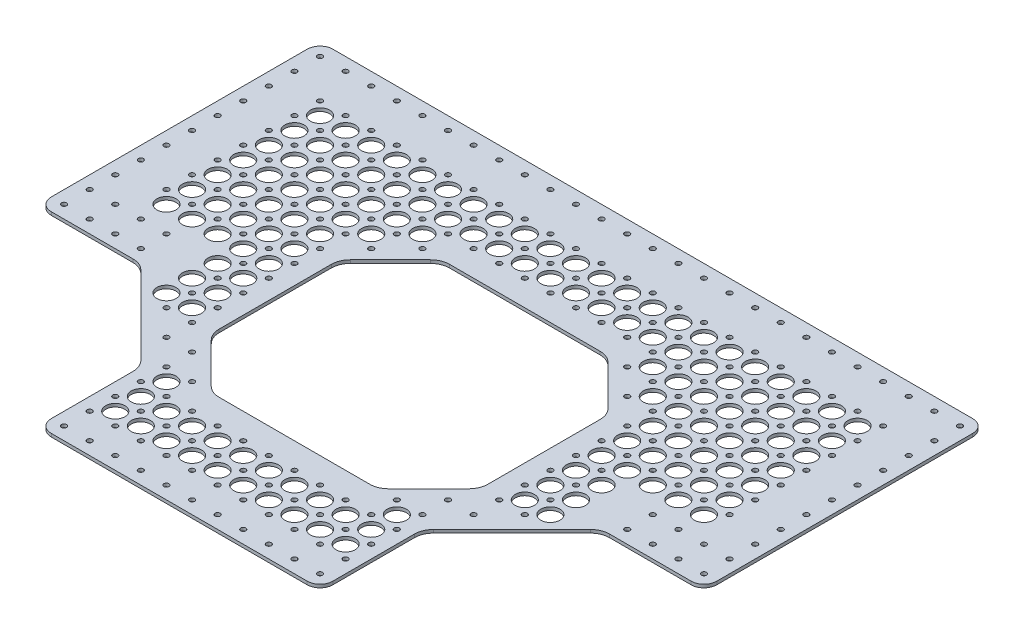
SolidWorks part; units mm, degrees
material "6061 Alloy"
ref_plane "Front Plane" through (0, 0, 0) normal (0, 0, 1) x (1, 0, 0)
ref_plane "Top Plane" through (0, 0, 0) normal (0, 1, 0) x (1, 0, 0)
ref_plane "Right Plane" through (0, 0, 0) normal (1, 0, 0) x (0, 0, -1)
sketch "Sketch1" plane through (0, 0, 0) normal (0, 1, 0) x (1, 0, 0)
  line L0 (0, 0) -> (0, 101.6)
  line L1 (0, 101.6) -> (279.4, 101.6)
  line L2 (279.4, 101.6) -> (279.4, 0)
  line L3 (279.4, 0) -> (368.3045, -88.9045)
  line L4 (368.3045, -88.9045) -> (469.9045, -88.9045)
  line L5 (469.9045, -88.9045) -> (469.9045, -419.1045)
  line L6 (469.9045, -419.1045) -> (368.3045, -419.1045)
  line L7 (368.3045, -419.1045) -> (279.4, -508.0091)
  line L8 (279.4, -508.0091) -> (279.4, -609.6091)
  line L9 (279.4, -609.6091) -> (0, -609.6091)
  line L10 (0, -609.6091) -> (0, -508.0091)
  line L11 (0, -508.0091) -> (-88.9045, -419.1045)
  line L12 (-88.9045, -419.1045) -> (-190.5045, -419.1045)
  line L13 (-190.5045, -419.1045) -> (-190.5045, -88.9045)
  line L14 (-190.5045, -88.9045) -> (-88.9045, -88.9045)
  line L15 (-88.9045, -88.9045) -> (0, 0)
  line L16 (-190.5045, -88.9045) -> (-177.8045, -88.9045)
  line L17 (-177.8045, -88.9045) -> (-177.8045, -419.1045) construction
  line L18 (-177.8045, -419.1045) -> (-190.5045, -419.1045)
  line L19 (-177.8045, -101.6045) -> (-177.8045, -127.0045) construction
  line L20 (139.7, -898.4) -> (139.7, 49101.6) construction
  line L21 (-966.4523, 88.9) -> (49033.5477, 88.9) construction
  line L22 (12.7, 88.9) -> (38.1, 88.9) construction
  line L23 (-1190.5045, -254.0045) -> (48809.4955, -254.0045) construction
  line L24 (-190.5045, -368.3045) -> (-88.9045, -368.3045) construction
  line L25 (-88.9045, -368.3045) -> (-88.9045, -419.1045) construction
  line L26 (-101.6045, -406.4045) -> (-127.0045, -406.4045) construction
  line L27 (-101.6045, -381.0045) -> (-127.0045, -381.0045) construction
  line L28 (-1102.5698, -114.3045) -> (48897.4302, -114.3045) construction
  line L29 (-1089.6596, -165.1045) -> (48910.3404, -165.1045) construction
  line L30 (-177.8045, -127.0045) -> (-152.4045, -127.0045) construction
  circle A0 centre (-177.8045, -101.6045) radius 2.54
  circle A1 centre (-177.8045, -127.0045) radius 2.54
  circle A2 centre (-177.8045, -152.4045) radius 2.54
  circle A3 centre (-177.8045, -177.8045) radius 2.54
  circle A4 centre (-177.8045, -203.2045) radius 2.54
  circle A5 centre (-177.8045, -228.6045) radius 2.54
  circle A6 centre (-177.8045, -254.0045) radius 2.54
  circle A7 centre (-177.8045, -279.4045) radius 2.54
  circle A8 centre (-177.8045, -304.8045) radius 2.54
  circle A9 centre (-177.8045, -330.2045) radius 2.54
  circle A10 centre (-177.8045, -355.6045) radius 2.54
  circle A11 centre (-177.8045, -381.0045) radius 2.54
  circle A12 centre (-177.8045, -406.4045) radius 2.54
  circle A13 centre (457.2045, -406.4045) radius 2.54
  circle A14 centre (457.2045, -381.0045) radius 2.54
  circle A15 centre (457.2045, -355.6045) radius 2.54
  circle A16 centre (457.2045, -330.2045) radius 2.54
  circle A17 centre (457.2045, -304.8045) radius 2.54
  circle A18 centre (457.2045, -279.4045) radius 2.54
  circle A19 centre (457.2045, -254.0045) radius 2.54
  circle A20 centre (457.2045, -228.6045) radius 2.54
  circle A21 centre (457.2045, -152.4045) radius 2.54
  circle A22 centre (457.2045, -177.8045) radius 2.54
  circle A23 centre (457.2045, -203.2045) radius 2.54
  circle A24 centre (457.2045, -127.0045) radius 2.54
  circle A25 centre (457.2045, -101.6045) radius 2.54
  circle A26 centre (12.7, 88.9) radius 2.54
  circle A27 centre (38.1, 88.9) radius 2.54
  circle A28 centre (63.5, 88.9) radius 2.54
  circle A29 centre (88.9, 88.9) radius 2.54
  circle A30 centre (114.3, 88.9) radius 2.54
  circle A31 centre (139.7, 88.9) radius 2.54
  circle A32 centre (165.1, 88.9) radius 2.54
  circle A33 centre (190.5, 88.9) radius 2.54
  circle A34 centre (215.9, 88.9) radius 2.54
  circle A35 centre (241.3, 88.9) radius 2.54
  circle A36 centre (266.7, 88.9) radius 2.54
  circle A37 centre (266.7, -596.9091) radius 2.54
  circle A38 centre (241.3, -596.9091) radius 2.54
  circle A39 centre (215.9, -596.9091) radius 2.54
  circle A40 centre (190.5, -596.9091) radius 2.54
  circle A41 centre (165.1, -596.9091) radius 2.54
  circle A42 centre (139.7, -596.9091) radius 2.54
  circle A43 centre (114.3, -596.9091) radius 2.54
  circle A44 centre (88.9, -596.9091) radius 2.54
  circle A45 centre (63.5, -596.9091) radius 2.54
  circle A46 centre (38.1, -596.9091) radius 2.54
  circle A47 centre (12.7, -596.9091) radius 2.54
  circle A48 centre (-101.6045, -381.0045) radius 2.54
  circle A49 centre (-101.6045, -406.4045) radius 2.54
  circle A50 centre (381.0045, -406.4045) radius 2.54
  circle A51 centre (381.0045, -381.0045) radius 2.54
  circle A52 centre (-127.0045, -406.4045) radius 2.54
  circle A53 centre (-152.4045, -406.4045) radius 2.54
  circle A54 centre (-127.0045, -381.0045) radius 2.54
  circle A55 centre (-152.4045, -381.0045) radius 2.54
  circle A56 centre (431.8045, -381.0045) radius 2.54
  circle A57 centre (406.4045, -381.0045) radius 2.54
  circle A58 centre (431.8045, -406.4045) radius 2.54
  circle A59 centre (406.4045, -406.4045) radius 2.54
  circle A60 centre (-152.4045, -127.0045) radius 2.54
  circle A61 centre (-152.4045, -152.4045) radius 2.54
  circle A62 centre (-127.0045, -127.0045) radius 2.54
  circle A63 centre (-127.0045, -152.4045) radius 2.54
  circle A64 centre (-101.6045, -127.0045) radius 2.54
  circle A65 centre (-101.6045, -152.4045) radius 2.54
  circle A66 centre (-76.2045, -127.0045) radius 2.54
  circle A67 centre (-76.2045, -152.4045) radius 2.54
  circle A68 centre (-50.8045, -127.0045) radius 2.54
  circle A69 centre (-50.8045, -152.4045) radius 2.54
  circle A70 centre (-25.4045, -127.0045) radius 2.54
  circle A71 centre (-25.4045, -152.4045) radius 2.54
  circle A72 centre (-0.0045, -127.0045) radius 2.54
  circle A73 centre (-0.0045, -152.4045) radius 2.54
  circle A74 centre (25.3955, -127.0045) radius 2.54
  circle A75 centre (25.3955, -152.4045) radius 2.54
  circle A76 centre (50.7955, -127.0045) radius 2.54
  circle A77 centre (50.7955, -152.4045) radius 2.54
  circle A78 centre (76.1955, -127.0045) radius 2.54
  circle A79 centre (76.1955, -152.4045) radius 2.54
  circle A80 centre (101.5955, -127.0045) radius 2.54
  circle A81 centre (101.5955, -152.4045) radius 2.54
  circle A82 centre (126.9955, -127.0045) radius 2.54
  circle A83 centre (126.9955, -152.4045) radius 2.54
  circle A84 centre (152.3955, -127.0045) radius 2.54
  circle A85 centre (152.3955, -152.4045) radius 2.54
  circle A86 centre (177.7955, -127.0045) radius 2.54
  circle A87 centre (177.7955, -152.4045) radius 2.54
  circle A88 centre (203.1955, -127.0045) radius 2.54
  circle A89 centre (203.1955, -152.4045) radius 2.54
  circle A90 centre (228.5955, -127.0045) radius 2.54
  circle A91 centre (228.5955, -152.4045) radius 2.54
  circle A92 centre (253.9955, -127.0045) radius 2.54
  circle A93 centre (253.9955, -152.4045) radius 2.54
  circle A94 centre (279.3955, -127.0045) radius 2.54
  circle A95 centre (279.3955, -152.4045) radius 2.54
  circle A96 centre (304.7955, -127.0045) radius 2.54
  circle A97 centre (304.7955, -152.4045) radius 2.54
  circle A98 centre (330.1955, -127.0045) radius 2.54
  circle A99 centre (330.1955, -152.4045) radius 2.54
  circle A100 centre (355.5955, -127.0045) radius 2.54
  circle A101 centre (355.5955, -152.4045) radius 2.54
  circle A102 centre (380.9955, -127.0045) radius 2.54
  circle A103 centre (380.9955, -152.4045) radius 2.54
  circle A104 centre (406.3955, -127.0045) radius 2.54
  circle A105 centre (406.3955, -152.4045) radius 2.54
  circle A106 centre (431.7955, -127.0045) radius 2.54
  circle A107 centre (431.7955, -152.4045) radius 2.54
  point P50 (139.7, 101.6)
  point P105 (-190.5045, -254.0045)
  dimension "D11" = 5.08
  dimension "D16" = 5.08
  dimension "D21" = 5.08
  dimension "D22" = 5.08
  dimension "D1" = 135
  dimension "D2" = 135
  dimension "D3" = 135
  dimension "D4" = 135
  dimension "D5" = 101.6
  dimension "D6" = 279.4
  dimension "D7" = 330.2
  dimension "D8" = 101.6
  dimension "D9" = 125.73
  dimension "D10" = 12.7
  dimension "D12" = 12.7
  dimension "D13" = 25.4
  dimension "D15" = 12.7
  dimension "D17" = 12.7
  dimension "D18" = 25.4
  dimension "D19" = 101.6
  dimension "D20" = 50.8
  dimension "D23" = 12.7
  dimension "D24" = 12.7
  dimension "D25" = 12.7
  dimension "D26" = 12.7
  dimension "D27" = 25.4
  dimension "D28" = 25.4
  dimension "D29" = 25.4
  dimension "D30" = 50.8
  dimension "D31" = 25.4
  dimension "D14" = 13
extrude "Boss-Extrude1" add sketch "Sketch1" along normal blind 3.175 contours L15 L14 L13 L12 L11 L10 L9 L8 L7 L6 L5 L4 L3 L2 L1 L0 A107 A106 A105 A104 A103 A102 A101 A100 A99 A98 A97 A96 A95 A94 A93 A92 region at (139.7, 0, 254.2329)
sketch "Sketch2" plane through (0, 0, -101.6) normal (0, 0, -1) x (-1, 0, 0)
  line L1 (-510.5355, -12.7) -> (251.4645, -12.7)
  line L2 (-510.5355, -12.7) -> (-510.5355, 12.7)
  line L3 (-510.5355, 12.7) -> (251.4645, 12.7)
  line L4 (251.4645, -12.7) -> (251.4645, 12.7)
  line L5 (-510.5355, -12.7) -> (251.4645, 12.7) construction
  line L6 (-510.5355, 12.7) -> (251.4645, -12.7) construction
  point P0 (-129.5355, 0)
  dimension "D1" = 762
  dimension "D2" = 25.4
extrude "Cut-Extrude1" cut sketch "Sketch2" against normal blind 241.3
sketch "Sketch3" plane through (0, 3.175, 0) normal (0, 1, 0) x (1, 0, 0)
  line L0 (-990.1544, -317.5045) -> (49009.8456, -317.5045) construction
  line L1 (-88.9045, -419.1045) -> (-190.5045, -419.1045) construction
  line L2 (-925.1076, -514.3545) -> (49074.8924, -514.3545) construction
  line L3 (139.7, 330.1887) -> (139.7, -609.6091) construction
  line L12 (6.35, -495.3045) -> (273.05, -495.3045)
  line L13 (279.4, -609.6091) -> (0, -609.6091) construction
  line L14 (0, -609.6091) -> (0, -508.0091) construction
  line L15 (6.35, -495.3045) -> (6.35, -317.5045)
  line L16 (6.35, -317.5045) -> (273.05, -317.5045)
  line L17 (273.05, -495.3045) -> (273.05, -317.5045)
  line L18 (6.35, -495.3045) -> (273.05, -317.5045) construction
  line L19 (6.35, -317.5045) -> (273.05, -495.3045) construction
  point P5 (139.7, -406.4045)
  point P9 (139.7, -139.7102)
  point P19 (139.7, -139.7102)
  dimension "D1" = 101.6
  dimension "D2" = 95.25
  dimension "D3" = 177.8
  dimension "D4" = 266.7
  dimension "D6" = 139.7
extrude "Cut-Extrude2" cut sketch "Sketch3" against normal blind 3.175
sketch "Sketch4" plane through (0, 3.175, 0) normal (0, 1, 0) x (1, 0, 0)
  line L0 (222.25, -495.3045) -> (273.05, -444.5045)
  line L1 (6.35, -495.3045) -> (273.05, -495.3045) construction
  line L2 (273.05, -495.3045) -> (273.05, -317.5045) construction
  line L3 (222.25, -495.3045) -> (273.05, -495.3045)
  line L4 (273.05, -495.3045) -> (273.05, -444.5045)
  line L5 (139.7, 369.2915) -> (139.7, -648.6915) construction
  line L7 (279.4, -508.0091) -> (279.4, -609.6091) construction
  line L8 (6.35, -495.3045) -> (6.35, -444.5045)
  line L9 (57.15, -495.3045) -> (6.35, -495.3045)
  line L10 (57.15, -495.3045) -> (6.35, -444.5045)
  point P10 (139.7, -139.7)
  dimension "D1" = 135
  dimension "D2" = 50.8
  dimension "D3" = 139.7
extrude "Boss-Extrude2" add sketch "Sketch4" against normal blind 3.175
sketch "Sketch7" plane through (0, 3.175, 0) normal (0, 1, 0) x (1, 0, 0)
  line L0 (6.35, -317.5045) -> (57.15, -266.7045)
  line L1 (57.15, -266.7045) -> (222.25, -266.7045)
  line L2 (222.25, -266.7045) -> (273.05, -317.5045)
  line L3 (273.05, -317.5045) -> (6.35, -317.5045) construction
  line L4 (6.35, -317.5045) -> (273.05, -317.5045)
  dimension "D1" = 165.1
  dimension "D2" = 45
  dimension "D3" = 45
extrude "Cut-Extrude3" cut sketch "Sketch7" against normal blind 3.175
sketch "Sketch8" plane through (0, 3.175, 0) normal (0, 1, 0) x (1, 0, 0)
  line L0 (-88.9045, -419.1045) -> (-190.5045, -419.1045) construction
  line L1 (0, -609.6091) -> (0, -508.0091) construction
  line L2 (12.7, -596.9091) -> (12.7, -571.5091) construction
  line L3 (279.4, -508.0091) -> (279.4, -609.6091) construction
  line L4 (76.1955, -533.4) -> (101.5955, -533.4) construction
  line L5 (292.1, -292.1091) -> (292.1, -317.5091) construction
  line L6 (-190.5045, -419.1045) -> (-190.5045, -139.7) construction
  line L7 (-190.5045, -139.7) -> (469.9045, -139.7) construction
  line L8 (-127.0045, -203.2) -> (-101.6045, -203.2) construction
  line L9 (-127.0045, -203.2) -> (-127.0045, -228.6) construction
  line L10 (-25.4045, -381) -> (-50.8045, -381) construction
  line L11 (50.7955, -533.4) -> (25.3955, -533.4) construction
  line L12 (228.5955, -533.4) -> (253.9955, -533.4) construction
  line L13 (25.3955, -533.4) -> (25.3955, -508) construction
  line L14 (253.9955, -533.4) -> (253.9955, -508) construction
  line L15 (330.1955, -431.8) -> (304.7955, -431.8) construction
  line L16 (304.7955, -279.4) -> (279.3955, -279.4) construction
  circle A0 centre (12.7, -596.9091) radius 2.54
  circle A1 centre (12.7, -571.5091) radius 2.54
  circle A2 centre (12.7, -546.1091) radius 2.54
  circle A3 centre (12.7, -520.7091) radius 2.54
  circle A4 centre (12.7, -495.3091) radius 2.54
  circle A5 centre (12.7, -469.9091) radius 2.54
  circle A12 centre (12.7, -292.1091) radius 2.54
  circle A13 centre (12.7, -266.7091) radius 2.54
  circle A14 centre (12.7, -241.3091) radius 2.54
  circle A15 centre (12.7, -215.9091) radius 2.54
  circle A16 centre (12.7, -190.5091) radius 2.54
  circle A19 centre (38.1, -190.5091) radius 2.54
  circle A20 centre (38.1, -215.9091) radius 2.54
  circle A21 centre (38.1, -241.3091) radius 2.54
  circle A22 centre (38.1, -266.7091) radius 2.54
  circle A30 centre (38.1, -495.3091) radius 2.54
  circle A31 centre (38.1, -520.7091) radius 2.54
  circle A32 centre (38.1, -546.1091) radius 2.54
  circle A33 centre (38.1, -571.5091) radius 2.54
  circle A35 centre (63.5, -190.5091) radius 2.54
  circle A36 centre (63.5, -215.9091) radius 2.54
  circle A37 centre (63.5, -241.3091) radius 2.54
  circle A47 centre (63.5, -520.7091) radius 2.54
  circle A48 centre (63.5, -546.1091) radius 2.54
  circle A49 centre (63.5, -571.5091) radius 2.54
  circle A51 centre (88.9, -190.5091) radius 2.54
  circle A52 centre (88.9, -215.9091) radius 2.54
  circle A53 centre (88.9, -241.3091) radius 2.54
  circle A63 centre (88.9, -520.7091) radius 2.54
  circle A64 centre (88.9, -546.1091) radius 2.54
  circle A65 centre (88.9, -571.5091) radius 2.54
  circle A67 centre (114.3, -190.5091) radius 2.54
  circle A68 centre (114.3, -215.9091) radius 2.54
  circle A69 centre (114.3, -241.3091) radius 2.54
  circle A79 centre (114.3, -520.7091) radius 2.54
  circle A80 centre (114.3, -546.1091) radius 2.54
  circle A81 centre (114.3, -571.5091) radius 2.54
  circle A83 centre (139.7, -190.5091) radius 2.54
  circle A84 centre (139.7, -215.9091) radius 2.54
  circle A85 centre (139.7, -241.3091) radius 2.54
  circle A95 centre (139.7, -520.7091) radius 2.54
  circle A96 centre (139.7, -546.1091) radius 2.54
  circle A97 centre (139.7, -571.5091) radius 2.54
  circle A99 centre (165.1, -190.5091) radius 2.54
  circle A100 centre (165.1, -215.9091) radius 2.54
  circle A101 centre (165.1, -241.3091) radius 2.54
  circle A111 centre (165.1, -520.7091) radius 2.54
  circle A112 centre (165.1, -546.1091) radius 2.54
  circle A113 centre (165.1, -571.5091) radius 2.54
  circle A115 centre (190.5, -190.5091) radius 2.54
  circle A116 centre (190.5, -215.9091) radius 2.54
  circle A117 centre (190.5, -241.3091) radius 2.54
  circle A127 centre (190.5, -520.7091) radius 2.54
  circle A128 centre (190.5, -546.1091) radius 2.54
  circle A129 centre (190.5, -571.5091) radius 2.54
  circle A131 centre (215.9, -190.5091) radius 2.54
  circle A132 centre (215.9, -215.9091) radius 2.54
  circle A133 centre (215.9, -241.3091) radius 2.54
  circle A143 centre (215.9, -520.7091) radius 2.54
  circle A144 centre (215.9, -546.1091) radius 2.54
  circle A145 centre (215.9, -571.5091) radius 2.54
  circle A147 centre (241.3, -190.5091) radius 2.54
  circle A148 centre (241.3, -215.9091) radius 2.54
  circle A149 centre (241.3, -241.3091) radius 2.54
  circle A150 centre (241.3, -266.7091) radius 2.54
  circle A158 centre (241.3, -495.3091) radius 2.54
  circle A159 centre (241.3, -520.7091) radius 2.54
  circle A160 centre (241.3, -546.1091) radius 2.54
  circle A161 centre (241.3, -571.5091) radius 2.54
  circle A163 centre (266.7, -190.5091) radius 2.54
  circle A164 centre (266.7, -215.9091) radius 2.54
  circle A165 centre (266.7, -241.3091) radius 2.54
  circle A166 centre (266.7, -266.7091) radius 2.54
  circle A167 centre (266.7, -292.1091) radius 2.54
  circle A173 centre (266.7, -469.9091) radius 2.54
  circle A174 centre (266.7, -495.3091) radius 2.54
  circle A175 centre (266.7, -520.7091) radius 2.54
  circle A176 centre (266.7, -546.1091) radius 2.54
  circle A177 centre (266.7, -571.5091) radius 2.54
  circle A179 centre (292.1, -190.5091) radius 2.54
  circle A180 centre (292.1, -215.9091) radius 2.54
  circle A181 centre (292.1, -241.3091) radius 2.54
  circle A182 centre (292.1, -266.7091) radius 2.54
  circle A183 centre (292.1, -292.1091) radius 2.54
  circle A189 centre (292.1, -469.9091) radius 2.54
  circle A195 centre (317.5, -190.5091) radius 2.54
  circle A196 centre (317.5, -215.9091) radius 2.54
  circle A197 centre (317.5, -241.3091) radius 2.54
  circle A198 centre (317.5, -266.7091) radius 2.54
  circle A199 centre (317.5, -292.1091) radius 2.54
  circle A211 centre (342.9, -190.5091) radius 2.54
  circle A212 centre (342.9, -215.9091) radius 2.54
  circle A213 centre (342.9, -241.3091) radius 2.54
  circle A214 centre (342.9, -266.7091) radius 2.54
  circle A215 centre (342.9, -292.1091) radius 2.54
  circle A227 centre (368.3, -190.5091) radius 2.54
  circle A228 centre (368.3, -215.9091) radius 2.54
  circle A229 centre (368.3, -241.3091) radius 2.54
  circle A230 centre (368.3, -266.7091) radius 2.54
  circle A231 centre (368.3, -292.1091) radius 2.54
  circle A243 centre (393.7, -190.5091) radius 2.54
  circle A244 centre (393.7, -215.9091) radius 2.54
  circle A245 centre (393.7, -241.3091) radius 2.54
  circle A246 centre (393.7, -266.7091) radius 2.54
  circle A247 centre (393.7, -292.1091) radius 2.54
  circle A259 centre (419.1, -190.5091) radius 2.54
  circle A260 centre (419.1, -215.9091) radius 2.54
  circle A261 centre (419.1, -241.3091) radius 2.54
  circle A262 centre (419.1, -266.7091) radius 2.54
  circle A263 centre (419.1, -292.1091) radius 2.54
  circle A291 centre (-12.7, -190.5091) radius 2.54
  circle A292 centre (-12.7, -215.9091) radius 2.54
  circle A293 centre (-12.7, -241.3091) radius 2.54
  circle A294 centre (-12.7, -266.7091) radius 2.54
  circle A295 centre (-12.7, -292.1091) radius 2.54
  circle A302 centre (-12.7, -469.9091) radius 2.54
  circle A308 centre (-38.1, -190.5091) radius 2.54
  circle A309 centre (-38.1, -215.9091) radius 2.54
  circle A310 centre (-38.1, -241.3091) radius 2.54
  circle A311 centre (-38.1, -266.7091) radius 2.54
  circle A312 centre (-38.1, -292.1091) radius 2.54
  circle A325 centre (-63.5, -190.5091) radius 2.54
  circle A326 centre (-63.5, -215.9091) radius 2.54
  circle A327 centre (-63.5, -241.3091) radius 2.54
  circle A328 centre (-63.5, -266.7091) radius 2.54
  circle A329 centre (-63.5, -292.1091) radius 2.54
  circle A342 centre (-88.9, -190.5091) radius 2.54
  circle A343 centre (-88.9, -215.9091) radius 2.54
  circle A344 centre (-88.9, -241.3091) radius 2.54
  circle A345 centre (-88.9, -266.7091) radius 2.54
  circle A346 centre (-88.9, -292.1091) radius 2.54
  circle A359 centre (-114.3, -190.5091) radius 2.54
  circle A360 centre (-114.3, -215.9091) radius 2.54
  circle A361 centre (-114.3, -241.3091) radius 2.54
  circle A362 centre (-114.3, -266.7091) radius 2.54
  circle A363 centre (-114.3, -292.1091) radius 2.54
  circle A376 centre (-139.7, -190.5091) radius 2.54
  circle A377 centre (-139.7, -215.9091) radius 2.54
  circle A378 centre (-139.7, -241.3091) radius 2.54
  circle A379 centre (-139.7, -266.7091) radius 2.54
  circle A380 centre (-139.7, -292.1091) radius 2.54
  circle A409 centre (-63.5, -495.3091) radius 2.54 [skipped]
  circle A410 centre (-63.5, -520.7091) radius 2.54 [skipped]
  circle A411 centre (-63.5, -546.1091) radius 2.54 [skipped]
  circle A412 centre (-63.5, -571.5091) radius 2.54 [skipped]
  circle A413 centre (-88.9, -469.9091) radius 2.54 [skipped]
  circle A414 centre (-88.9, -495.3091) radius 2.54 [skipped]
  circle A415 centre (-88.9, -520.7091) radius 2.54 [skipped]
  circle A416 centre (-88.9, -546.1091) radius 2.54 [skipped]
  circle A417 centre (-88.9, -571.5091) radius 2.54 [skipped]
  circle A418 centre (-114.3, -469.9091) radius 2.54 [skipped]
  circle A419 centre (-114.3, -495.3091) radius 2.54 [skipped]
  circle A420 centre (-114.3, -520.7091) radius 2.54 [skipped]
  circle A421 centre (-114.3, -546.1091) radius 2.54 [skipped]
  circle A422 centre (-114.3, -571.5091) radius 2.54 [skipped]
  circle A423 centre (-139.7, -469.9091) radius 2.54 [skipped]
  circle A424 centre (-139.7, -495.3091) radius 2.54 [skipped]
  circle A425 centre (-139.7, -520.7091) radius 2.54 [skipped]
  circle A426 centre (-139.7, -546.1091) radius 2.54 [skipped]
  circle A427 centre (-139.7, -571.5091) radius 2.54 [skipped]
  circle A428 centre (-165.1, -469.9091) radius 2.54 [skipped]
  circle A429 centre (-165.1, -495.3091) radius 2.54 [skipped]
  circle A430 centre (-165.1, -520.7091) radius 2.54 [skipped]
  circle A431 centre (-165.1, -546.1091) radius 2.54 [skipped]
  circle A432 centre (-165.1, -571.5091) radius 2.54 [skipped]
  circle A433 centre (-63.5, -469.9091) radius 2.54 [skipped]
  circle A434 centre (-12.7, -495.3091) radius 2.54 [skipped]
  circle A435 centre (-12.7, -520.7091) radius 2.54 [skipped]
  circle A436 centre (-12.7, -546.1091) radius 2.54 [skipped]
  circle A437 centre (-12.7, -571.5091) radius 2.54 [skipped]
  circle A438 centre (-38.1, -495.3091) radius 2.54 [skipped]
  circle A439 centre (-38.1, -520.7091) radius 2.54 [skipped]
  circle A440 centre (-38.1, -546.1091) radius 2.54 [skipped]
  circle A441 centre (-38.1, -571.5091) radius 2.54 [skipped]
  circle A442 centre (-127.0045, -203.2) radius 9.525
  circle A443 centre (-101.6045, -203.2) radius 9.525
  circle A444 centre (-76.2045, -203.2) radius 9.525
  circle A445 centre (-50.8045, -203.2) radius 9.525
  circle A446 centre (-25.4045, -203.2) radius 9.525
  circle A447 centre (-0.0045, -203.2) radius 9.525
  circle A448 centre (25.3955, -203.2) radius 9.525
  circle A449 centre (50.7955, -203.2) radius 9.525
  circle A450 centre (76.1955, -203.2) radius 9.525
  circle A451 centre (-38.1, -469.9091) radius 2.54 [skipped]
  circle A452 centre (101.5955, -203.2) radius 9.525
  circle A453 centre (126.9955, -203.2) radius 9.525
  circle A454 centre (152.3955, -203.2) radius 9.525
  circle A455 centre (177.7955, -203.2) radius 9.525
  circle A456 centre (203.1955, -203.2) radius 9.525
  circle A457 centre (228.5955, -203.2) radius 9.525
  circle A458 centre (253.9955, -203.2) radius 9.525
  circle A459 centre (279.3955, -203.2) radius 9.525
  circle A460 centre (304.7955, -203.2) radius 9.525
  circle A461 centre (330.1955, -203.2) radius 9.525
  circle A462 centre (355.5955, -203.2) radius 9.525
  circle A463 centre (380.9955, -203.2) radius 9.525
  circle A464 centre (406.3955, -203.2) radius 9.525
  circle A467 centre (-101.6045, -228.6) radius 9.525
  circle A468 centre (-76.2045, -228.6) radius 9.525
  circle A469 centre (-50.8045, -228.6) radius 9.525
  circle A470 centre (-25.4045, -228.6) radius 9.525
  circle A471 centre (-0.0045, -228.6) radius 9.525
  circle A472 centre (25.3955, -228.6) radius 9.525
  circle A473 centre (50.7955, -228.6) radius 9.525
  circle A474 centre (76.1955, -228.6) radius 9.525
  circle A475 centre (101.5955, -228.6) radius 9.525
  circle A476 centre (126.9955, -228.6) radius 9.525
  circle A477 centre (152.3955, -228.6) radius 9.525
  circle A478 centre (177.7955, -228.6) radius 9.525
  circle A479 centre (203.1955, -228.6) radius 9.525
  circle A480 centre (228.5955, -228.6) radius 9.525
  circle A481 centre (253.9955, -228.6) radius 9.525
  circle A482 centre (279.3955, -228.6) radius 9.525
  circle A483 centre (304.7955, -228.6) radius 9.525
  circle A484 centre (330.1955, -228.6) radius 9.525
  circle A485 centre (355.5955, -228.6) radius 9.525
  circle A486 centre (380.9955, -228.6) radius 9.525
  circle A487 centre (406.3955, -228.6) radius 9.525
  circle A490 centre (-101.6045, -254) radius 9.525
  circle A491 centre (-76.2045, -254) radius 9.525
  circle A492 centre (-50.8045, -254) radius 9.525
  circle A493 centre (-25.4045, -254) radius 9.525
  circle A494 centre (-0.0045, -254) radius 9.525
  circle A495 centre (25.3955, -254) radius 9.525
  circle A497 centre (38.1, -292.1091) radius 2.54 [skipped]
  circle A498 centre (63.5, -292.1091) radius 2.54 [skipped]
  circle A499 centre (88.9, -292.1091) radius 2.54 [skipped]
  circle A500 centre (114.3, -292.1091) radius 2.54 [skipped]
  circle A501 centre (139.7, -292.1091) radius 2.54 [skipped]
  circle A502 centre (165.1, -292.1091) radius 2.54 [skipped]
  circle A503 centre (190.5, -292.1091) radius 2.54 [skipped]
  circle A504 centre (241.3, -292.1091) radius 2.54 [skipped]
  circle A505 centre (215.9, -292.1091) radius 2.54 [skipped]
  circle A506 centre (63.5, -266.7091) radius 2.54 [skipped]
  circle A507 centre (88.9, -266.7091) radius 2.54 [skipped]
  circle A508 centre (114.3, -266.7091) radius 2.54 [skipped]
  circle A509 centre (139.7, -266.7091) radius 2.54 [skipped]
  circle A510 centre (165.1, -266.7091) radius 2.54 [skipped]
  circle A511 centre (215.9, -266.7091) radius 2.54 [skipped]
  circle A512 centre (190.5, -266.7091) radius 2.54 [skipped]
  circle A518 centre (12.7, -419.1091) radius 2.54 [skipped]
  circle A519 centre (12.7, -393.7091) radius 2.54 [skipped]
  circle A520 centre (12.7, -368.3091) radius 2.54 [skipped]
  circle A521 centre (12.7, -342.9091) radius 2.54 [skipped]
  circle A522 centre (12.7, -317.5091) radius 2.54 [skipped]
  circle A523 centre (12.7, -444.5091) radius 2.54 [skipped]
  circle A524 centre (292.1, -546.1091) radius 2.54 [skipped]
  circle A525 centre (292.1, -571.5091) radius 2.54 [skipped]
  circle A526 centre (317.5, -520.7091) radius 2.54 [skipped]
  circle A527 centre (317.5, -546.1091) radius 2.54 [skipped]
  circle A528 centre (317.5, -571.5091) radius 2.54 [skipped]
  circle A529 centre (342.9, -520.7091) radius 2.54 [skipped]
  circle A530 centre (342.9, -546.1091) radius 2.54 [skipped]
  circle A531 centre (342.9, -571.5091) radius 2.54 [skipped]
  circle A532 centre (368.3, -520.7091) radius 2.54 [skipped]
  circle A533 centre (368.3, -546.1091) radius 2.54 [skipped]
  circle A534 centre (368.3, -571.5091) radius 2.54 [skipped]
  circle A535 centre (393.7, -520.7091) radius 2.54 [skipped]
  circle A536 centre (393.7, -546.1091) radius 2.54 [skipped]
  circle A537 centre (393.7, -571.5091) radius 2.54 [skipped]
  circle A538 centre (419.1, -520.7091) radius 2.54 [skipped]
  circle A539 centre (419.1, -546.1091) radius 2.54 [skipped]
  circle A540 centre (419.1, -571.5091) radius 2.54 [skipped]
  circle A541 centre (444.5, -520.7091) radius 2.54 [skipped]
  circle A542 centre (444.5, -546.1091) radius 2.54 [skipped]
  circle A543 centre (444.5, -571.5091) radius 2.54 [skipped]
  circle A544 centre (292.1, -520.7091) radius 2.54 [skipped]
  circle A545 centre (317.5, -495.3091) radius 2.54 [skipped]
  circle A546 centre (342.9, -495.3091) radius 2.54 [skipped]
  circle A547 centre (368.3, -495.3091) radius 2.54 [skipped]
  circle A548 centre (393.7, -495.3091) radius 2.54 [skipped]
  circle A549 centre (419.1, -495.3091) radius 2.54 [skipped]
  circle A550 centre (444.5, -495.3091) radius 2.54 [skipped]
  circle A551 centre (292.1, -495.3091) radius 2.54 [skipped]
  circle A552 centre (317.5, -469.9091) radius 2.54 [skipped]
  circle A553 centre (342.9, -469.9091) radius 2.54 [skipped]
  circle A554 centre (368.3, -469.9091) radius 2.54 [skipped]
  circle A555 centre (393.7, -469.9091) radius 2.54 [skipped]
  circle A556 centre (419.1, -469.9091) radius 2.54 [skipped]
  circle A557 centre (444.5, -469.9091) radius 2.54 [skipped]
  circle A558 centre (38.1, -469.9091) radius 2.54 [skipped]
  circle A559 centre (63.5, -469.9091) radius 2.54 [skipped]
  circle A560 centre (88.9, -469.9091) radius 2.54 [skipped]
  circle A561 centre (114.3, -469.9091) radius 2.54 [skipped]
  circle A562 centre (139.7, -469.9091) radius 2.54 [skipped]
  circle A563 centre (165.1, -469.9091) radius 2.54 [skipped]
  circle A564 centre (190.5, -469.9091) radius 2.54 [skipped]
  circle A565 centre (215.9, -469.9091) radius 2.54 [skipped]
  circle A566 centre (241.3, -469.9091) radius 2.54 [skipped]
  circle A567 centre (63.5, -495.3091) radius 2.54 [skipped]
  circle A568 centre (88.9, -495.3091) radius 2.54 [skipped]
  circle A569 centre (114.3, -495.3091) radius 2.54 [skipped]
  circle A570 centre (139.7, -495.3091) radius 2.54 [skipped]
  circle A571 centre (165.1, -495.3091) radius 2.54 [skipped]
  circle A572 centre (190.5, -495.3091) radius 2.54 [skipped]
  circle A573 centre (215.9, -495.3091) radius 2.54 [skipped]
  circle A575 centre (-139.7, -317.5091) radius 2.54
  circle A576 centre (-114.3, -317.5091) radius 2.54
  circle A577 centre (-88.9, -317.5091) radius 2.54
  circle A578 centre (-63.5, -317.5091) radius 2.54
  circle A579 centre (-38.1, -317.5091) radius 2.54
  circle A580 centre (-12.7, -317.5091) radius 2.54
  circle A582 centre (-139.7, -342.9091) radius 2.54
  circle A583 centre (-114.3, -342.9091) radius 2.54
  circle A584 centre (-88.9, -342.9091) radius 2.54
  circle A585 centre (-63.5, -342.9091) radius 2.54
  circle A586 centre (-38.1, -342.9091) radius 2.54
  circle A587 centre (-12.7, -342.9091) radius 2.54
  circle A593 centre (-38.1, -368.3091) radius 2.54
  circle A594 centre (-12.7, -368.3091) radius 2.54
  circle A600 centre (-38.1, -393.7091) radius 2.54
  circle A601 centre (-12.7, -393.7091) radius 2.54
  circle A607 centre (-38.1, -419.1091) radius 2.54
  circle A608 centre (-12.7, -419.1091) radius 2.54
  circle A614 centre (-38.1, -444.5091) radius 2.54
  circle A615 centre (-12.7, -444.5091) radius 2.54
  circle A616 centre (292.1, -317.5091) radius 2.54
  circle A617 centre (317.5, -317.5091) radius 2.54
  circle A618 centre (342.9, -317.5091) radius 2.54
  circle A619 centre (368.3, -317.5091) radius 2.54
  circle A620 centre (393.7, -317.5091) radius 2.54
  circle A621 centre (419.1, -317.5091) radius 2.54
  circle A623 centre (292.1, -342.9091) radius 2.54
  circle A624 centre (317.5, -342.9091) radius 2.54
  circle A625 centre (342.9, -342.9091) radius 2.54
  circle A626 centre (368.3, -342.9091) radius 2.54
  circle A627 centre (393.7, -342.9091) radius 2.54
  circle A628 centre (419.1, -342.9091) radius 2.54
  circle A630 centre (292.1, -368.3091) radius 2.54
  circle A631 centre (317.5, -368.3091) radius 2.54
  circle A637 centre (292.1, -393.7091) radius 2.54
  circle A638 centre (317.5, -393.7091) radius 2.54
  circle A644 centre (292.1, -419.1091) radius 2.54
  circle A645 centre (317.5, -419.1091) radius 2.54
  circle A651 centre (292.1, -444.5091) radius 2.54
  circle A652 centre (317.5, -444.5091) radius 2.54
  circle A658 centre (342.9, -444.5091) radius 2.54 [skipped]
  circle A659 centre (393.7, -444.5091) radius 2.54 [skipped]
  circle A660 centre (419.1, -444.5091) radius 2.54 [skipped]
  circle A661 centre (101.5955, -533.4) radius 9.525
  circle A662 centre (368.3, -444.5091) radius 2.54 [skipped]
  circle A663 centre (393.7, -419.1091) radius 2.54 [skipped]
  circle A664 centre (419.1, -419.1091) radius 2.54 [skipped]
  circle A665 centre (126.9955, -533.4) radius 9.525
  circle A666 centre (368.3, -419.1091) radius 2.54 [skipped]
  circle A667 centre (393.7, -393.7091) radius 2.54 [skipped]
  circle A668 centre (419.1, -393.7091) radius 2.54 [skipped]
  circle A669 centre (152.3955, -533.4) radius 9.525
  circle A670 centre (177.7955, -533.4) radius 9.525
  circle A671 centre (-139.7, -444.5091) radius 2.54 [skipped]
  circle A672 centre (-114.3, -444.5091) radius 2.54 [skipped]
  circle A673 centre (-63.5, -444.5091) radius 2.54 [skipped]
  circle A674 centre (-88.9, -444.5091) radius 2.54 [skipped]
  circle A675 centre (203.1955, -533.4) radius 9.525
  circle A676 centre (-139.7, -393.7091) radius 2.54 [skipped]
  circle A677 centre (-114.3, -393.7091) radius 2.54 [skipped]
  circle A678 centre (228.5955, -533.4) radius 9.525
  circle A679 centre (-139.7, -419.1091) radius 2.54 [skipped]
  circle A680 centre (-114.3, -419.1091) radius 2.54 [skipped]
  circle A681 centre (-88.9, -419.1091) radius 2.54 [skipped]
  circle A685 centre (279.3955, -254) radius 9.525
  circle A686 centre (304.7955, -254) radius 9.525
  circle A687 centre (330.1955, -254) radius 9.525
  circle A688 centre (355.5955, -254) radius 9.525
  circle A689 centre (380.9955, -254) radius 9.525
  circle A690 centre (406.3955, -254) radius 9.525
  circle A693 centre (-101.6045, -279.4) radius 9.525
  circle A694 centre (-76.2045, -279.4) radius 9.525
  circle A695 centre (-50.8045, -279.4) radius 9.525
  circle A696 centre (-25.4045, -279.4) radius 9.525
  circle A697 centre (-0.0045, -279.4) radius 9.525
  circle A709 centre (304.7955, -279.4) radius 9.525
  circle A710 centre (330.1955, -279.4) radius 9.525
  circle A711 centre (355.5955, -279.4) radius 9.525
  circle A712 centre (380.9955, -279.4) radius 9.525
  circle A713 centre (406.3955, -279.4) radius 9.525
  circle A716 centre (-101.6045, -304.8) radius 9.525
  circle A717 centre (-76.2045, -304.8) radius 9.525
  circle A718 centre (-50.8045, -304.8) radius 9.525
  circle A719 centre (-25.4045, -304.8) radius 9.525
  circle A723 centre (76.1955, -304.8) radius 9.525 [skipped]
  circle A724 centre (101.5955, -304.8) radius 9.525 [skipped]
  circle A725 centre (126.9955, -304.8) radius 9.525 [skipped]
  circle A726 centre (152.3955, -304.8) radius 9.525 [skipped]
  circle A727 centre (177.7955, -304.8) radius 9.525 [skipped]
  circle A728 centre (203.1955, -304.8) radius 9.525 [skipped]
  circle A729 centre (228.5955, -304.8) radius 9.525 [skipped]
  circle A730 centre (253.9955, -304.8) radius 9.525 [skipped]
  circle A733 centre (330.1955, -304.8) radius 9.525
  circle A734 centre (355.5955, -304.8) radius 9.525
  circle A735 centre (380.9955, -304.8) radius 9.525
  circle A736 centre (406.3955, -304.8) radius 9.525
  circle A739 centre (-101.6045, -330.2) radius 9.525
  circle A740 centre (-76.2045, -330.2) radius 9.525
  circle A741 centre (-50.8045, -330.2) radius 9.525
  circle A742 centre (-25.4045, -330.2) radius 9.525
  circle A745 centre (50.7955, -330.2) radius 9.525 [skipped]
  circle A746 centre (76.1955, -330.2) radius 9.525 [skipped]
  circle A747 centre (101.5955, -330.2) radius 9.525 [skipped]
  circle A748 centre (126.9955, -330.2) radius 9.525 [skipped]
  circle A749 centre (152.3955, -330.2) radius 9.525 [skipped]
  circle A750 centre (177.7955, -330.2) radius 9.525 [skipped]
  circle A751 centre (203.1955, -330.2) radius 9.525 [skipped]
  circle A752 centre (228.5955, -330.2) radius 9.525 [skipped]
  circle A753 centre (253.9955, -330.2) radius 9.525 [skipped]
  circle A754 centre (279.3955, -330.2) radius 9.525 [skipped]
  circle A756 centre (330.1955, -330.2) radius 9.525
  circle A757 centre (355.5955, -330.2) radius 9.525
  circle A758 centre (380.9955, -330.2) radius 9.525
  circle A759 centre (406.3955, -330.2) radius 9.525
  circle A762 centre (-101.6045, -355.6) radius 9.525
  circle A763 centre (-76.2045, -355.6) radius 9.525
  circle A764 centre (-50.8045, -355.6) radius 9.525
  circle A765 centre (-25.4045, -355.6) radius 9.525
  circle A768 centre (50.7955, -355.6) radius 9.525 [skipped]
  circle A769 centre (76.1955, -355.6) radius 9.525 [skipped]
  circle A770 centre (101.5955, -355.6) radius 9.525 [skipped]
  circle A771 centre (126.9955, -355.6) radius 9.525 [skipped]
  circle A772 centre (152.3955, -355.6) radius 9.525 [skipped]
  circle A773 centre (177.7955, -355.6) radius 9.525 [skipped]
  circle A774 centre (203.1955, -355.6) radius 9.525 [skipped]
  circle A775 centre (228.5955, -355.6) radius 9.525 [skipped]
  circle A776 centre (253.9955, -355.6) radius 9.525 [skipped]
  circle A777 centre (279.3955, -355.6) radius 9.525 [skipped]
  circle A779 centre (330.1955, -355.6) radius 9.525
  circle A780 centre (355.5955, -355.6) radius 9.525
  circle A781 centre (380.9955, -355.6) radius 9.525
  circle A782 centre (406.3955, -355.6) radius 9.525
  circle A788 centre (-25.4045, -381) radius 9.525
  circle A791 centre (50.7955, -381) radius 9.525 [skipped]
  circle A792 centre (76.1955, -381) radius 9.525 [skipped]
  circle A799 centre (253.9955, -381) radius 9.525 [skipped]
  circle A800 centre (279.3955, -381) radius 9.525 [skipped]
  circle A802 centre (330.1955, -381) radius 9.525
  circle A811 centre (-25.4045, -406.4) radius 9.525
  circle A814 centre (50.7955, -406.4) radius 9.525 [skipped]
  circle A815 centre (76.1955, -406.4) radius 9.525 [skipped]
  circle A825 centre (330.1955, -406.4) radius 9.525
  circle A834 centre (-25.4045, -431.8) radius 9.525
  circle A837 centre (50.7955, -431.8) radius 9.525 [skipped]
  circle A838 centre (76.1955, -431.8) radius 9.525 [skipped]
  circle A848 centre (330.1955, -431.8) radius 9.525
  circle A856 centre (-50.8045, -457.2) radius 9.525 [skipped]
  circle A860 centre (50.7955, -457.2) radius 9.525 [skipped]
  circle A861 centre (76.1955, -457.2) radius 9.525 [skipped]
  circle A873 centre (380.9955, -457.2) radius 9.525 [skipped]
  circle A880 centre (-25.4045, -482.6) radius 9.525 [skipped]
  circle A883 centre (50.7955, -482.6) radius 9.525 [skipped]
  circle A884 centre (76.1955, -482.6) radius 9.525 [skipped]
  circle A892 centre (279.3955, -482.6) radius 9.525 [skipped]
  circle A895 centre (355.5955, -482.6) radius 9.525 [skipped]
  circle A904 centre (-0.0045, -508) radius 9.525 [skipped]
  circle A914 centre (253.9955, -508) radius 9.525 [skipped]
  circle A917 centre (330.1955, -508) radius 9.525 [skipped]
  circle A928 centre (25.3955, -533.4) radius 9.525 [skipped]
  circle A929 centre (50.7955, -533.4) radius 9.525
  circle A930 centre (76.1955, -533.4) radius 9.525
  circle A939 centre (304.7955, -533.4) radius 9.525 [skipped]
  circle A951 centre (25.3955, -558.8) radius 9.525 [skipped]
  circle A952 centre (50.7955, -558.8) radius 9.525
  circle A953 centre (76.1955, -558.8) radius 9.525
  circle A954 centre (101.5955, -558.8) radius 9.525
  circle A955 centre (126.9955, -558.8) radius 9.525
  circle A956 centre (152.3955, -558.8) radius 9.525
  circle A957 centre (177.7955, -558.8) radius 9.525
  circle A958 centre (203.1955, -558.8) radius 9.525
  circle A959 centre (228.5955, -558.8) radius 9.525
  circle A962 centre (304.7955, -558.8) radius 9.525 [skipped]
  circle A985 centre (-50.8045, -381) radius 9.525
  circle A992 centre (-127.0045, -228.6) radius 9.525
  circle A993 centre (-127.0045, -254) radius 9.525
  circle A994 centre (-127.0045, -279.4) radius 9.525
  circle A995 centre (-127.0045, -304.8) radius 9.525
  circle A996 centre (-127.0045, -330.2) radius 9.525
  circle A997 centre (-127.0045, -355.6) radius 9.525
  circle A1007 centre (76.1955, -508) radius 9.525 [skipped]
  circle A1008 centre (25.3955, -355.6) radius 9.525 [skipped]
  circle A1009 centre (25.3955, -381) radius 9.525 [skipped]
  circle A1010 centre (25.3955, -406.4) radius 9.525 [skipped]
  circle A1011 centre (25.3955, -431.8) radius 9.525 [skipped]
  circle A1012 centre (25.3955, -457.2) radius 9.525 [skipped]
  circle A1013 centre (279.3955, -457.2) radius 9.525 [skipped]
  circle A1014 centre (101.5955, -381) radius 9.525 [skipped]
  circle A1015 centre (126.9955, -381) radius 9.525 [skipped]
  circle A1016 centre (152.3955, -381) radius 9.525 [skipped]
  circle A1017 centre (177.7955, -381) radius 9.525 [skipped]
  circle A1018 centre (203.1955, -381) radius 9.525 [skipped]
  circle A1019 centre (228.5955, -381) radius 9.525 [skipped]
  circle A1020 centre (101.5955, -406.4) radius 9.525 [skipped]
  circle A1021 centre (126.9955, -406.4) radius 9.525 [skipped]
  circle A1022 centre (152.3955, -406.4) radius 9.525 [skipped]
  circle A1023 centre (177.7955, -406.4) radius 9.525 [skipped]
  circle A1024 centre (203.1955, -406.4) radius 9.525 [skipped]
  circle A1025 centre (228.5955, -406.4) radius 9.525 [skipped]
  circle A1026 centre (101.5955, -431.8) radius 9.525 [skipped]
  circle A1027 centre (126.9955, -431.8) radius 9.525 [skipped]
  circle A1028 centre (152.3955, -431.8) radius 9.525 [skipped]
  circle A1029 centre (177.7955, -431.8) radius 9.525 [skipped]
  circle A1030 centre (203.1955, -431.8) radius 9.525 [skipped]
  circle A1031 centre (228.5955, -431.8) radius 9.525 [skipped]
  circle A1032 centre (101.5955, -457.2) radius 9.525 [skipped]
  circle A1033 centre (126.9955, -457.2) radius 9.525 [skipped]
  circle A1034 centre (152.3955, -457.2) radius 9.525 [skipped]
  circle A1035 centre (177.7955, -457.2) radius 9.525 [skipped]
  circle A1036 centre (203.1955, -457.2) radius 9.525 [skipped]
  circle A1037 centre (228.5955, -457.2) radius 9.525 [skipped]
  circle A1038 centre (101.5955, -482.6) radius 9.525 [skipped]
  circle A1039 centre (126.9955, -482.6) radius 9.525 [skipped]
  circle A1040 centre (152.3955, -482.6) radius 9.525 [skipped]
  circle A1041 centre (177.7955, -482.6) radius 9.525 [skipped]
  circle A1042 centre (203.1955, -482.6) radius 9.525 [skipped]
  circle A1043 centre (228.5955, -482.6) radius 9.525 [skipped]
  circle A1044 centre (101.5955, -508) radius 9.525 [skipped]
  circle A1045 centre (126.9955, -508) radius 9.525 [skipped]
  circle A1046 centre (152.3955, -508) radius 9.525 [skipped]
  circle A1047 centre (177.7955, -508) radius 9.525 [skipped]
  circle A1048 centre (203.1955, -508) radius 9.525 [skipped]
  circle A1049 centre (228.5955, -508) radius 9.525 [skipped]
  circle A1050 centre (253.9955, -406.4) radius 9.525 [skipped]
  circle A1051 centre (279.3955, -406.4) radius 9.525 [skipped]
  circle A1052 centre (253.9955, -431.8) radius 9.525 [skipped]
  circle A1053 centre (253.9955, -457.2) radius 9.525 [skipped]
  circle A1054 centre (279.3955, -431.8) radius 9.525 [skipped]
  circle A1055 centre (253.9955, -482.6) radius 9.525 [skipped]
  circle A1056 centre (304.7955, -355.6) radius 9.525 [skipped]
  circle A1057 centre (304.7955, -381) radius 9.525 [skipped]
  circle A1058 centre (304.7955, -406.4) radius 9.525 [skipped]
  circle A1059 centre (304.7955, -431.8) radius 9.525 [skipped]
  circle A1060 centre (304.7955, -457.2) radius 9.525 [skipped]
  circle A1061 centre (-127.0045, -406.4) radius 9.525 [skipped]
  circle A1062 centre (-101.6045, -406.4) radius 9.525 [skipped]
  circle A1063 centre (-76.2045, -406.4) radius 9.525 [skipped]
  circle A1064 centre (-76.2045, -431.8) radius 9.525 [skipped]
  circle A1065 centre (-101.6045, -431.8) radius 9.525 [skipped]
  circle A1066 centre (-127.0045, -431.8) radius 9.525 [skipped]
  circle A1067 centre (-50.8045, -406.4) radius 9.525
  circle A1068 centre (-139.7, -368.3091) radius 2.54 [skipped]
  circle A1069 centre (-114.3, -368.3091) radius 2.54 [skipped]
  circle A1070 centre (-88.9, -368.3091) radius 2.54 [skipped]
  circle A1071 centre (-88.9, -393.7091) radius 2.54 [skipped]
  circle A1072 centre (-101.6045, -457.2) radius 9.525 [skipped]
  circle A1073 centre (-76.2045, -457.2) radius 9.525 [skipped]
  circle A1074 centre (-101.6045, -482.6) radius 9.525 [skipped]
  circle A1075 centre (-76.2045, -482.6) radius 9.525 [skipped]
  circle A1076 centre (-127.0045, -457.2) radius 9.525 [skipped]
  circle A1077 centre (-127.0045, -482.6) radius 9.525 [skipped]
  circle A1078 centre (-50.8045, -482.6) radius 9.525 [skipped]
  circle A1079 centre (-101.6045, -533.4) radius 9.525 [skipped]
  circle A1080 centre (-76.2045, -533.4) radius 9.525 [skipped]
  circle A1081 centre (-50.8045, -533.4) radius 9.525 [skipped]
  circle A1082 centre (-25.4045, -533.4) radius 9.525 [skipped]
  circle A1083 centre (-0.0045, -533.4) radius 9.525 [skipped]
  circle A1084 centre (-101.6045, -558.8) radius 9.525 [skipped]
  circle A1085 centre (-76.2045, -558.8) radius 9.525 [skipped]
  circle A1086 centre (-50.8045, -558.8) radius 9.525 [skipped]
  circle A1087 centre (-25.4045, -558.8) radius 9.525 [skipped]
  circle A1088 centre (-0.0045, -558.8) radius 9.525 [skipped]
  circle A1089 centre (-50.8045, -431.8) radius 9.525
  circle A1090 centre (25.3955, -533.4) radius 9.525
  circle A1091 centre (25.3955, -558.8) radius 9.525
  circle A1092 centre (253.9955, -533.4) radius 9.525
  circle A1093 centre (-127.0045, -533.4) radius 9.525 [skipped]
  circle A1094 centre (-127.0045, -558.8) radius 9.525 [skipped]
  circle A1095 centre (253.9955, -558.8) radius 9.525
  circle A1096 centre (25.3955, -508) radius 9.525
  circle A1097 centre (-101.6045, -508) radius 9.525 [skipped]
  circle A1098 centre (-76.2045, -508) radius 9.525 [skipped]
  circle A1099 centre (-50.8045, -508) radius 9.525 [skipped]
  circle A1100 centre (-25.4045, -508) radius 9.525 [skipped]
  circle A1101 centre (-127.0045, -508) radius 9.525 [skipped]
  circle A1102 centre (355.5955, -533.4) radius 9.525 [skipped]
  circle A1103 centre (380.9955, -533.4) radius 9.525 [skipped]
  circle A1104 centre (406.3955, -533.4) radius 9.525 [skipped]
  circle A1105 centre (253.9955, -508) radius 9.525
  circle A1106 centre (304.7955, -431.8) radius 9.525
  circle A1107 centre (330.1955, -558.8) radius 9.525 [skipped]
  circle A1108 centre (355.5955, -558.8) radius 9.525 [skipped]
  circle A1109 centre (380.9955, -558.8) radius 9.525 [skipped]
  circle A1110 centre (406.3955, -558.8) radius 9.525 [skipped]
  circle A1111 centre (304.7955, -406.4) radius 9.525
  circle A1112 centre (304.7955, -381) radius 9.525
  circle A1113 centre (304.7955, -355.6) radius 9.525
  circle A1114 centre (304.7955, -330.2) radius 9.525
  circle A1115 centre (304.7955, -304.8) radius 9.525
  circle A1116 centre (279.3955, -279.4) radius 9.525
  circle A1117 centre (253.9955, -254) radius 9.525
  circle A1119 centre (330.1955, -533.4) radius 9.525 [skipped]
  circle A1120 centre (380.9955, -508) radius 9.525 [skipped]
  circle A1121 centre (406.3955, -508) radius 9.525 [skipped]
  circle A1124 centre (355.5955, -508) radius 9.525 [skipped]
  circle A1126 centre (380.9955, -482.6) radius 9.525 [skipped]
  circle A1127 centre (406.3955, -482.6) radius 9.525 [skipped]
  circle A1129 centre (406.3955, -457.2) radius 9.525 [skipped]
  circle A1132 centre (406.3955, -431.8) radius 9.525 [skipped]
  circle A1135 centre (406.3955, -406.4) radius 9.525 [skipped]
  circle A1138 centre (368.3, -368.3091) radius 2.54 [skipped]
  circle A1139 centre (368.3, -393.7091) radius 2.54 [skipped]
  circle A1140 centre (393.7, -368.3091) radius 2.54 [skipped]
  circle A1141 centre (419.1, -368.3091) radius 2.54 [skipped]
  circle A1143 centre (380.9955, -406.4) radius 9.525 [skipped]
  circle A1144 centre (380.9955, -431.8) radius 9.525 [skipped]
  circle A1145 centre (342.9, -368.3091) radius 2.54 [skipped]
  circle A1146 centre (342.9, -393.7091) radius 2.54 [skipped]
  circle A1147 centre (342.9, -419.1091) radius 2.54 [skipped]
  circle A1148 centre (-50.8045, -406.4) radius 9.525 [skipped]
  circle A1149 centre (-50.8045, -431.8) radius 9.525 [skipped]
  circle A1150 centre (-63.5, -419.1091) radius 2.54 [skipped]
  circle A1151 centre (-63.5, -393.7091) radius 2.54 [skipped]
  circle A1152 centre (-63.5, -368.3091) radius 2.54 [skipped]
  circle A1177 centre (12.7, -165.1091) radius 2.54 [skipped]
  circle A1178 centre (-165.1, -215.9091) radius 2.54 [skipped]
  circle A1179 centre (-165.1, -241.3091) radius 2.54 [skipped]
  circle A1180 centre (-165.1, -266.7091) radius 2.54 [skipped]
  circle A1181 centre (-165.1, -292.1091) radius 2.54 [skipped]
  circle A1182 centre (-165.1, -190.5091) radius 2.54 [skipped]
  circle A1183 centre (444.5, -215.9091) radius 2.54 [skipped]
  circle A1184 centre (444.5, -241.3091) radius 2.54 [skipped]
  circle A1185 centre (444.5, -266.7091) radius 2.54 [skipped]
  circle A1186 centre (444.5, -292.1091) radius 2.54 [skipped]
  circle A1187 centre (444.5, -190.5091) radius 2.54 [skipped]
  circle A1188 centre (25.3955, -330.2) radius 9.525 [skipped]
  circle A1189 centre (50.7955, -304.8) radius 9.525 [skipped]
  circle A1190 centre (101.5955, -279.4) radius 9.525 [skipped]
  circle A1191 centre (126.9955, -279.4) radius 9.525 [skipped]
  circle A1192 centre (152.3955, -279.4) radius 9.525 [skipped]
  circle A1193 centre (177.7955, -279.4) radius 9.525 [skipped]
  circle A1194 centre (203.1955, -279.4) radius 9.525 [skipped]
  circle A1195 centre (228.5955, -279.4) radius 9.525 [skipped]
  circle A1196 centre (76.1955, -279.4) radius 9.525 [skipped]
  circle A1197 centre (253.9955, -279.4) radius 9.525 [skipped]
  circle A1198 centre (279.3955, -304.8) radius 9.525 [skipped]
  circle A1199 centre (304.7955, -330.2) radius 9.525 [skipped]
  circle A1200 centre (101.5955, -533.4) radius 9.525 [skipped]
  circle A1201 centre (126.9955, -533.4) radius 9.525 [skipped]
  circle A1202 centre (152.3955, -533.4) radius 9.525 [skipped]
  circle A1203 centre (203.1955, -533.4) radius 9.525 [skipped]
  circle A1204 centre (228.5955, -533.4) radius 9.525 [skipped]
  circle A1205 centre (253.9955, -533.4) radius 9.525 [skipped]
  circle A1206 centre (177.7955, -533.4) radius 9.525 [skipped]
  circle A1207 centre (279.3955, -508) radius 9.525 [skipped]
  circle A1208 centre (304.7955, -482.6) radius 9.525 [skipped]
  circle A1209 centre (50.7955, -508) radius 9.525 [skipped]
  circle A1210 centre (25.3955, -482.6) radius 9.525 [skipped]
  circle A1211 centre (-25.4045, -457.2) radius 9.525 [skipped]
  circle A1212 centre (-0.0045, -482.6) radius 9.525 [skipped]
  circle A1213 centre (25.3955, -508) radius 9.525 [skipped]
  circle A1214 centre (-127.0045, -381) radius 9.525 [skipped]
  circle A1215 centre (-76.2045, -381) radius 9.525 [skipped]
  circle A1216 centre (-101.6045, -381) radius 9.525 [skipped]
  circle A1217 centre (406.3955, -381) radius 9.525 [skipped]
  circle A1220 centre (380.9955, -381) radius 9.525 [skipped]
  circle A1221 centre (-50.8045, -381) radius 9.525 [skipped]
  circle A1222 centre (25.3955, -304.8) radius 9.525 [skipped]
  circle A1223 centre (50.7955, -279.4) radius 9.525 [skipped]
  circle A1224 centre (101.5955, -254) radius 9.525 [skipped]
  circle A1225 centre (126.9955, -254) radius 9.525 [skipped]
  circle A1226 centre (152.3955, -254) radius 9.525 [skipped]
  circle A1227 centre (177.7955, -254) radius 9.525 [skipped]
  circle A1228 centre (203.1955, -254) radius 9.525 [skipped]
  circle A1229 centre (228.5955, -254) radius 9.525 [skipped]
  circle A1230 centre (253.9955, -254) radius 9.525 [skipped]
  circle A1231 centre (279.3955, -279.4) radius 9.525 [skipped]
  circle A1232 centre (304.7955, -304.8) radius 9.525 [skipped]
  circle A1233 centre (304.7955, -508) radius 9.525 [skipped]
  circle A1234 centre (330.1955, -482.6) radius 9.525 [skipped]
  circle A1235 centre (355.5955, -457.2) radius 9.525 [skipped]
  circle A1236 centre (-0.0045, -330.2) radius 9.525 [skipped]
  circle A1237 centre (-0.0045, -355.6) radius 9.525 [skipped]
  circle A1238 centre (-0.0045, -381) radius 9.525 [skipped]
  circle A1239 centre (-0.0045, -406.4) radius 9.525 [skipped]
  circle A1240 centre (-0.0045, -431.8) radius 9.525 [skipped]
  circle A1241 centre (-0.0045, -457.2) radius 9.525 [skipped]
  circle A1242 centre (355.5955, -381) radius 9.525 [skipped]
  circle A1243 centre (355.5955, -406.4) radius 9.525 [skipped]
  circle A1244 centre (355.5955, -431.8) radius 9.525 [skipped]
  circle A1245 centre (330.1955, -457.2) radius 9.525 [skipped]
  circle A1246 centre (76.1955, -254) radius 9.525 [skipped]
  circle A1247 centre (50.7955, -254) radius 9.525 [skipped]
  circle A1248 centre (25.3955, -279.4) radius 9.525 [skipped]
  circle A1249 centre (-0.0045, -304.8) radius 9.525 [skipped]
  circle A1250 centre (279.3955, -558.8) radius 9.525 [skipped]
  circle A1251 centre (279.3955, -533.4) radius 9.525 [skipped]
  circle A1252 centre (253.9955, -533.4) radius 9.525 [skipped]
  circle A1253 centre (253.9955, -558.8) radius 9.525 [skipped]
  dimension "D3" = 5.08
  dimension "D13" = 19.05
  dimension "D19" = 25.4
  dimension "D31" = 25.4
  dimension "D32" = 25.4
  dimension "D1" = 18
  dimension "D2" = 12.7
  dimension "D4" = 25.4
  dimension "D6" = 50.8045
  dimension "D7" = 12.7
  dimension "D9" = 76.1955
  dimension "D10" = 25.4
  dimension "D14" = 63.5
  dimension "D15" = 63.5
  dimension "D17" = 25.4
  dimension "D20" = 25.4
  dimension "D21" = 25.4
  dimension "D23" = 25.4
  dimension "D24" = 25.4
  dimension "D26" = 25.4
  dimension "D28" = 25.4
  dimension "D29" = 25.4
  dimension "D30" = 25.4
  dimension "D5" = 18
  dimension "D8" = 8
  dimension "D12" = 7
  dimension "D11" = 7
  dimension "D18" = 22
  dimension "D16" = 15
  dimension "D22" = 8
  dimension "D25" = 2
  dimension "D27" = 2
extrude "Cut-Extrude5" cut sketch "Sketch8" against normal blind 3.175
fillet "Fillet1" radius 12.7 6 edges at (-190.5045, 1.5875, 419.1045) (0, 1.5875, 609.6091) (279.4, 1.5875, 609.6091) (469.9045, 1.5875, 419.1045) (469.9045, 1.5875, 139.7) (-190.5045, 1.5875, 139.7)
fillet "Fillet2" radius 19.05 12 edges at (0, 1.5875, 508.0091) (-88.9045, 1.5875, 419.1045) (222.25, 1.5875, 266.7045) (273.05, 1.5875, 317.5045) (273.05, 1.5875, 444.5045) (222.25, 1.5875, 495.3045) (57.15, 1.5875, 495.3045) (6.35, 1.5875, 317.5045) (57.15, 1.5875, 266.7045) (6.35, 1.5875, 444.5045) (279.4, 1.5875, 508.0091) (368.3045, 1.5875, 419.1045)
sketch "Sketch9" plane through (0, 3.175, 0) normal (0, -1, 0) x (1, 0, 0)
  line L0 (-1189.9314, 139.7) -> (48810.0686, 139.7) construction
  line L1 (-190.5045, -847.6558) -> (-190.5045, 49152.3442) construction
  line L2 (-177.8045, 139.7) -> (457.2045, 139.7) construction
  line L3 (-190.5045, 406.4045) -> (-190.5045, 152.4) construction
  point P3 (-190.5045, 139.7)
  point P5 (-443.3994, 105.3572)
sketch "Sketch11" plane through (0, 0, 0) normal (0, -1, 0) x (1, 0, 0)
  line L0 (6.35, 325.3953) -> (6.35, 436.6138) construction
  line L1 (214.3592, 266.7045) -> (65.0408, 266.7045) construction
  line L4 (273.05, 436.6138) -> (273.05, 325.3953) construction
  circle A0 centre (57.15, 330.2045) radius 2.54
  circle A1 centre (57.15, 431.8045) radius 2.54
  circle A2 centre (222.25, 330.2045) radius 2.54
  circle A3 centre (110.0667, 330.2045) radius 2.54
  circle A4 centre (110.0667, 431.8045) radius 2.54
  circle A5 centre (222.25, 431.8045) radius 2.54
  circle A6 centre (162.9833, 330.2045) radius 2.54
  circle A7 centre (162.9833, 431.8045) radius 2.54
  point P22 (0, 0)
  point P23 (0, 0)
  point P24 (0, 0)
  dimension "D1" = 5.08
  dimension "D2" = 50.8
  dimension "D3" = 101.6
  dimension "D5" = 50.8
  dimension "D7" = 52.9167
  dimension "D4" = 63.5
  dimension "D6" = 52.9167
